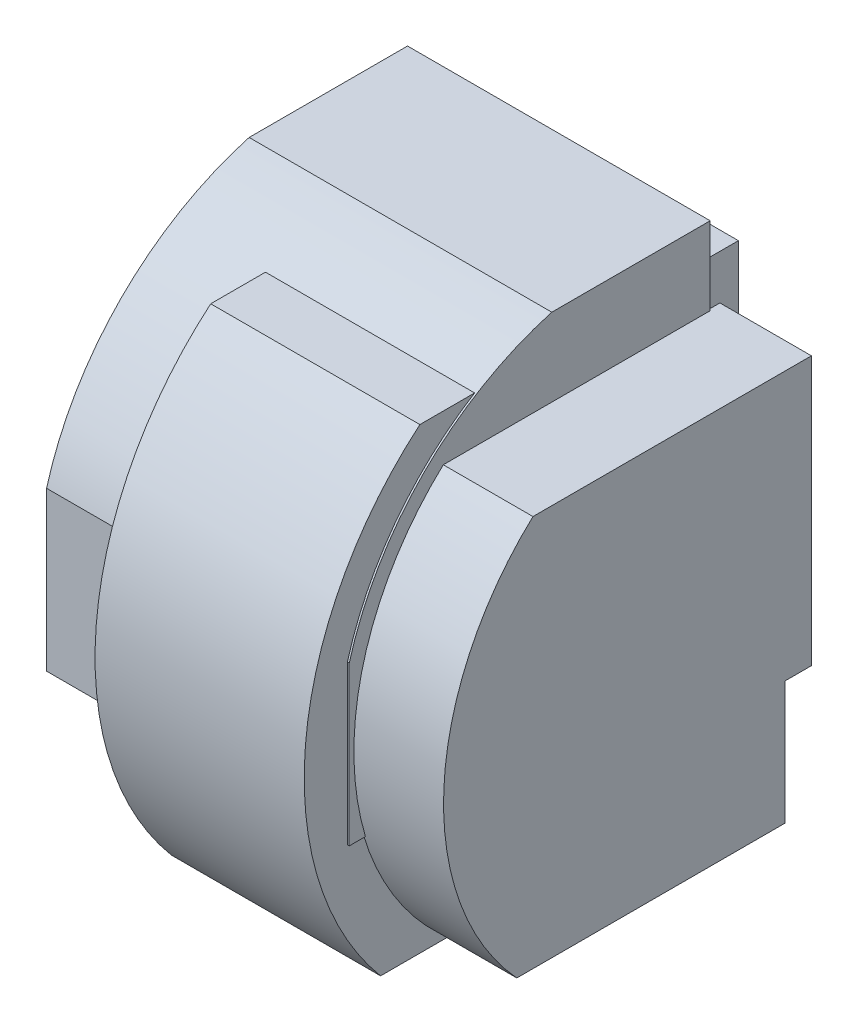
SolidWorks part; units mm, degrees
ref_plane "Front Plane" through (0, 0, 0) normal (0, 0, 1) x (1, 0, 0)
ref_plane "Top Plane" through (0, 0, 0) normal (0, 1, 0) x (1, 0, 0)
ref_plane "Right Plane" through (0, 0, 0) normal (1, 0, 0) x (0, 0, -1)
sketch "Sketch2" plane through (9.0434, 0, 0) normal (-1, 0, 0) x (0, 0, 1)
  point P0 (0, 0)
  line B0 (21.5519, 6.0579) -> (-10.8966, 6.0579)
  line B1 (21.5519, 6.0579) -> (21.5519, -6.0579)
  line B2 (21.5519, -6.0579) -> (-10.8966, -6.0579)
  line B3 (-10.8966, 6.0579) -> (-10.8966, -6.0579)
  line B4 (-6.0579, 21.5519) -> (-6.0579, -10.8966)
  line B5 (-6.0579, 21.5519) -> (6.0579, 21.5519)
  line B6 (6.0579, 21.5519) -> (6.0579, -10.8966)
  line B7 (-6.0579, -10.8966) -> (6.0579, -10.8966)
sketch_block_instance "Block1-1"
sketch_block "Block1"
sketch_block_instance "Block1-2"
sketch "Sketch3" plane through (9.0434, 0, 0) normal (-1, 0, 0) x (0, 0, 1)
  line L1 (-6.0579, 21.5519) -> (-6.0579, -10.8966) construction
  line L3 (-6.0579, 21.5519) -> (-6.0579, 6.0579)
  line L4 (-6.0579, 21.5519) -> (6.0579, 21.5519) construction
  line L5 (-6.0579, 21.5519) -> (6.0579, 21.5519)
  line L6 (-6.0579, -10.8966) -> (6.0579, -10.8966) construction
  line L7 (-6.0579, -10.8966) -> (6.0579, -10.8966)
  line L8 (6.0579, 21.5519) -> (6.0579, -10.8966) construction
  line L9 (6.0579, -6.0579) -> (6.0579, -10.8966)
  line L10 (-6.0579, 6.0579) -> (-10.8966, 6.0579)
  line L11 (21.5519, 6.0579) -> (21.5519, -6.0579) construction
  line L12 (21.5519, -6.0579) -> (-10.8966, -6.0579) construction
  line L13 (21.5519, 6.0579) -> (21.5519, -6.0579)
  line L14 (21.5519, -6.0579) -> (6.0579, -6.0579)
  arc A0 (6.0579, 21.5519) -> (21.5519, 6.0579) centre (0, 0) cw
  arc A1 (-6.0579, -10.8966) -> (-10.8966, 6.0579) centre (0, 0) cw
  point P14 (-11.3321, 5.1979)
extrude "Boss-Extrude1" add sketch "Sketch3" against normal up to surface (23.1521 mm away)
sketch "Sketch4" plane through (16.0538, 0, 0) normal (-1, 0, 0) x (0, 0, 1)
  point P0 (0, 0)
  line B0 (-8.3579, -16.0079) -> (19.0132, -16.0079)
  line B1 (-8.3579, -16.0079) -> (-8.3579, 8.3579)
  line B2 (-8.3579, 8.3579) -> (19.0132, 8.3579)
  line B3 (19.0132, -16.0079) -> (19.0132, 8.3579)
  line B4 (16.0079, -8.3579) -> (16.0079, 19.0132)
  line B5 (16.0079, -8.3579) -> (-8.3579, -8.3579)
  line B6 (-8.3579, -8.3579) -> (-8.3579, 19.0132)
  line B7 (16.0079, 19.0132) -> (-8.3579, 19.0132)
sketch_block_instance "Block2-1"
sketch_block "Block2"
sketch_block_instance "Block2-2"
sketch "Sketch5" plane through (16.0538, 0, 0) normal (-1, 0, 0) x (0, 0, 1)
  line L0 (16.0079, 19.0132) -> (-8.3579, 19.0132) construction
  line L1 (-8.3579, -8.3579) -> (-8.3579, 19.0132) construction
  line L2 (16.0079, 19.0132) -> (-8.3579, 19.0132)
  line L3 (-8.3579, -8.3579) -> (-8.3579, 19.0132)
  line L4 (-8.3579, -16.0079) -> (19.0132, -16.0079) construction
  line L6 (-8.3579, -16.0079) -> (19.0132, -16.0079)
  line L8 (-8.3579, -8.3579) -> (-8.3579, -16.0079)
  arc A1 (16.0079, 19.0132) -> (19.0132, -16.0079) centre (0, 0) cw
  point P8 (18.7391, -16.3279)
extrude "Boss-Extrude2" add sketch "Sketch5" against normal up to surface (16 mm away)
sketch "Sketch6" plane through (32.0538, 0, 0) normal (1, 0, 0) x (0, 0, -1)
  point P0 (0, 0)
  line B0 (-15.5926, -14.3579) -> (4.9374, -14.3579)
  line B1 (-15.5926, -14.3579) -> (-15.5926, 6.9421)
  line B2 (-15.5926, 6.9421) -> (4.9374, 6.9421)
  line B3 (4.9374, -14.3579) -> (4.9374, 6.9421)
  line B4 (3.5623, -3.0579) -> (-14.2177, -3.0579) construction
  line B5 (-14.357, 15.5935) -> (-14.3582, -4.9365)
  line B6 (-14.357, 15.5935) -> (6.943, 15.5922)
  line B7 (6.943, 15.5922) -> (6.9418, -4.9378)
  line B8 (-14.3582, -4.9365) -> (6.9418, -4.9378)
  line B9 (-3.0581, -3.5622) -> (-3.0571, 14.2178) construction
sketch_block_instance "Block3-1"
sketch_block "Block3" parameters "D1"=10
sketch_block_instance "Block3-2"
sketch "Sketch7" plane through (32.0538, 0, 0) normal (1, 0, 0) x (0, 0, -1)
  line L0 (-15.5926, -14.3579) -> (4.9374, -14.3579) construction
  line L1 (4.9374, -14.3579) -> (4.9374, 6.9421) construction
  line L2 (-14.3582, -4.9365) -> (6.9418, -4.9378) construction
  line L3 (6.943, 15.5922) -> (6.9418, -4.9378) construction
  line L4 (-14.357, 15.5935) -> (6.943, 15.5922) construction
  line L5 (-15.5926, -14.3579) -> (4.9374, -14.3579)
  line L6 (4.9374, -14.3579) -> (4.9374, -4.9376)
  line L7 (4.9374, -4.9376) -> (6.9418, -4.9378)
  line L8 (6.943, 15.5922) -> (6.9418, -4.9378)
  line L9 (-14.357, 15.5935) -> (6.943, 15.5922)
  arc A0 (-14.357, 15.5935) -> (-15.5926, -14.3579) centre (0, 0) ccw
  point P3 (-15.5926, -14.3579)
extrude "Boss-Extrude3" add sketch "Sketch7" along normal up to surface (7 mm away)
